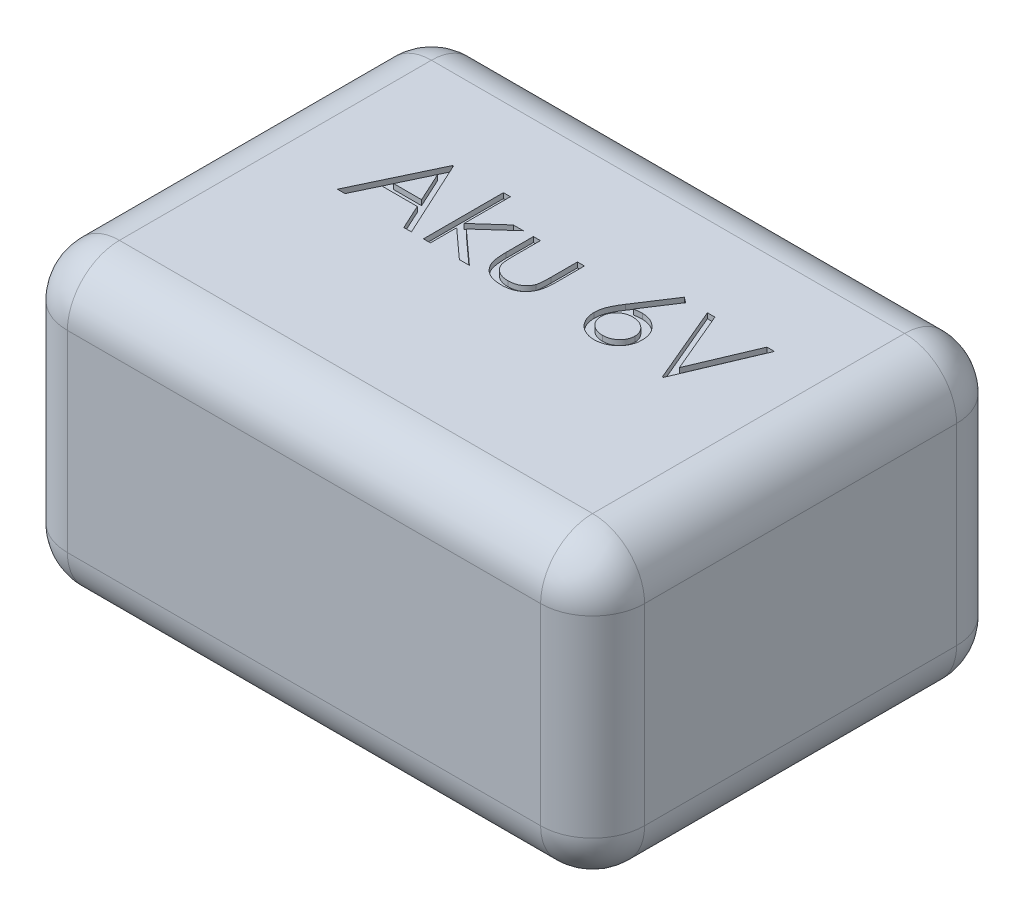
SolidWorks part; units mm, degrees
ref_plane "Front" through (0, 0, 0) normal (0, 0, 1) x (1, 0, 0)
ref_plane "Top" through (0, 0, 0) normal (0, 1, 0) x (1, 0, 0)
ref_plane "Right" through (0, 0, 0) normal (1, 0, 0) x (0, 0, -1)
sketch "Sketch1" plane through (0, 0, 0) normal (0, 1, 0) x (1, 0, 0)
  line L1 (-55.5, 40) -> (55.5, 40)
  line L2 (-55.5, 40) -> (-55.5, -40)
  line L3 (-55.5, -40) -> (55.5, -40)
  line L4 (55.5, 40) -> (55.5, -40)
  dimension "D1" = 80
  dimension "D2" = 111
  dimension "D3" = 55.5
  dimension "D6" = 40
extrude "Boss-Extrude1" add sketch "Sketch1" along normal blind 57
fillet "Fillet1" radius 10 12 edges at (0, 0, 40) (55.5, 0, 0) (0, 0, -40) (-55.5, 0, 0) (0, 57, -40) (55.5, 57, 0) (0, 57, 40) (-55.5, 57, 0) (55.5, 28.5, -40) (55.5, 28.5, 40) (-55.5, 28.5, -40) (-55.5, 28.5, 40)
sketch "Sketch2" plane through (0, 57, 0) normal (0, 1, 0) x (1, 0, 0)
  line L2 (45.5, -30) -> (45.5, 30) construction
  line L3 (45.5, 30) -> (-45.5, 30) construction
  text T0 "Aku 6V\r\n" font "Century Gothic" height 15
  dimension "D1" = 79.3239
  dimension "D2" = 30.5192
extrude "Cut-Extrude1" cut sketch "Sketch2" against normal blind 1
ref_point "Point1"
ref_point "Point2"
ref_plane "Plane1" through (0, -20, 0) normal (0, -1, 0) x (-1, 0, 0)
sketch "Sketch4" plane through (0, -20, 0) normal (0, -1, 0) x (-1, 0, 0)
  line L0 (-7.5, 17.793) -> (-13.6105, 17.793) construction
  line L6 (28.9949, 0) -> (28.9949, 12.2077)
  line L7 (-28.9949, 0) -> (28.9949, 0)
  line L8 (-28.9949, 12.2077) -> (-28.9949, 0)
  line L9 (-21.0626, 35.5861) -> (-28.9949, 12.2077)
  line L10 (21.0626, 35.5861) -> (-21.0626, 35.5861)
  line L11 (28.9949, 12.2077) -> (21.0626, 35.5861)
  line L12 (28.9949, 0) -> (28.9949, 12.2077) construction
  line L13 (-28.9949, 0) -> (28.9949, 0) construction
  line L14 (-28.9949, 12.2077) -> (-28.9949, 0) construction
  line L15 (-21.0626, 35.5861) -> (-28.9949, 12.2077) construction
  line L16 (21.0626, 35.5861) -> (-21.0626, 35.5861) construction
  line L17 (28.9949, 12.2077) -> (21.0626, 35.5861) construction
  circle A0 centre (0, 17.793) radius 7.5
  dimension "D2" = 15
  dimension "D3" = 17.793
  dimension "D1" = 0
sketch "Sketch6" plane through (0, 0, 0) normal (0, -1, 0) x (1, 0, 0)
  line L2 (15, 0) -> (18.782, 0) construction
  line L3 (28.9949, 0) -> (-28.9949, 0) construction
  circle A0 centre (0, 0) radius 15
  dimension "D1" = 30
loft "Loft1" add profiles "Sketch6", "Sketch4" connector at (15, 0, 0) connector at (7.5, -20, -17.793)
fillet "Fillet2" radius 10 1 edges at (14.5973, 0, -3.4526)
